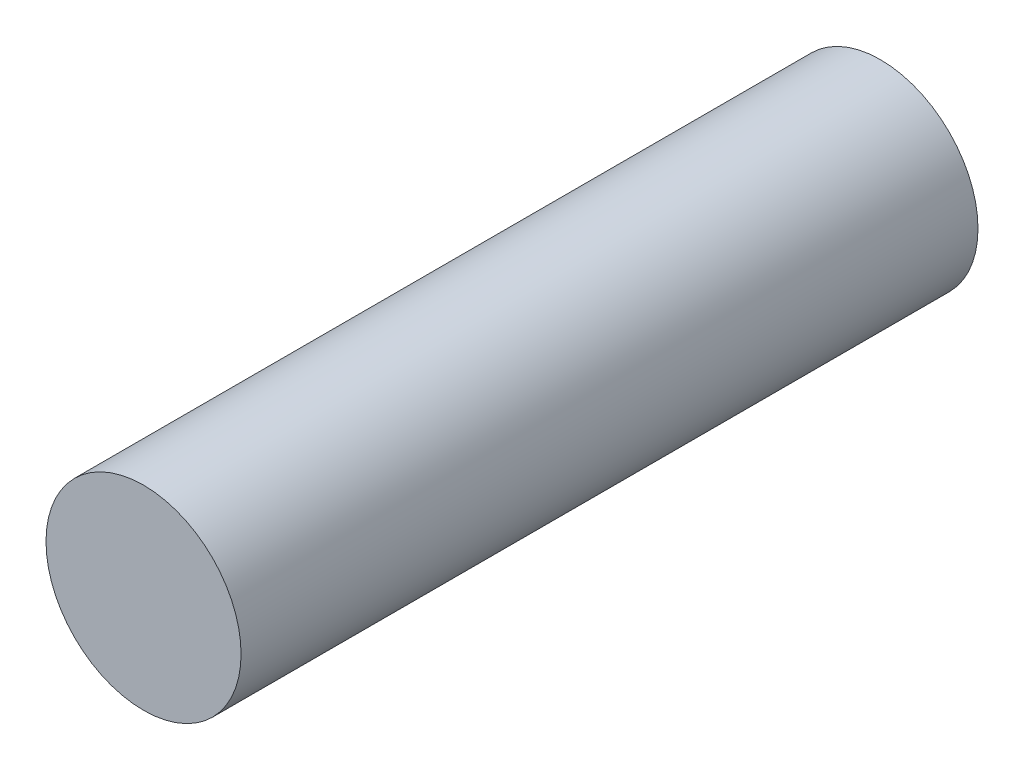
SolidWorks part; units mm, degrees
ref_plane "Front Plane" through (0, 0, 0) normal (0, 0, 1) x (1, 0, 0)
ref_plane "Top Plane" through (0, 0, 0) normal (0, 1, 0) x (1, 0, 0)
ref_plane "Right Plane" through (0, 0, 0) normal (1, 0, 0) x (0, 0, -1)
sketch "Sketch1" plane through (0, 0, 0) normal (0, 0, 1) x (1, 0, 0)
  circle A0 centre (0, 0) radius 2.25
  dimension "D1" = 4.5
extrude "Boss-Extrude1" add sketch "Sketch1" along normal mid plane 17
sketch "Sketch2" plane through (0, 0, 0) normal (0, 0, 1) x (1, 0, 0)
  circle A0 centre (0, 0) radius 2.5 construction
  dimension "D1" = 5
